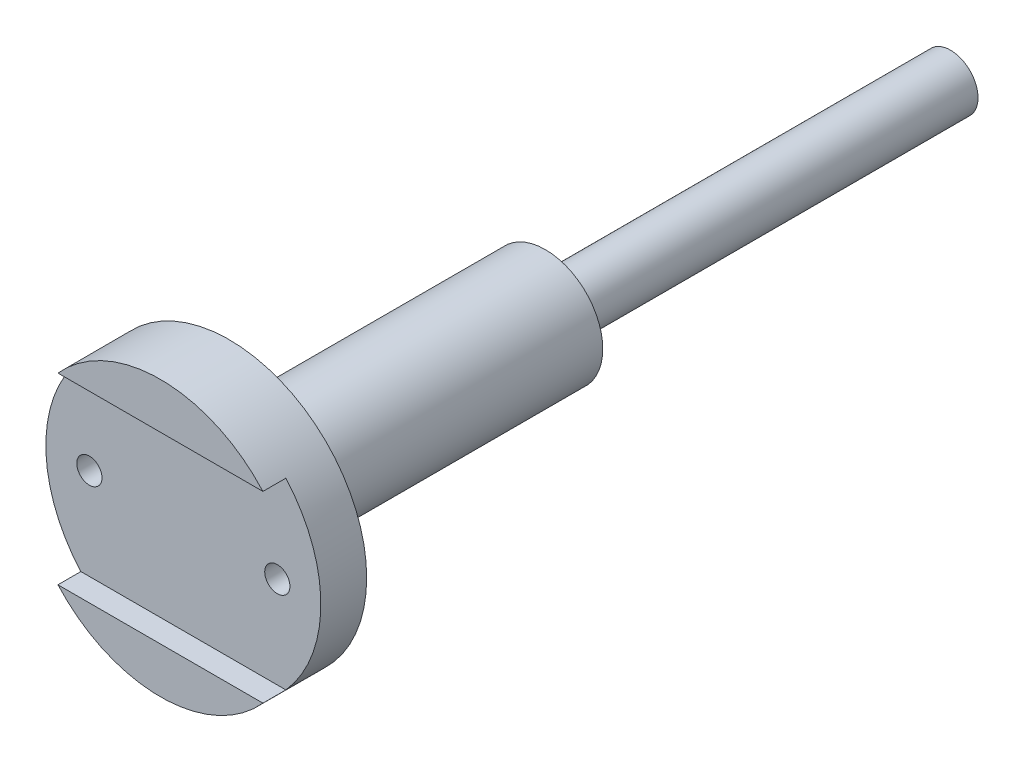
SolidWorks part; units mm, degrees
ref_plane "Plan de face" through (0, 0, 0) normal (0, 0, 1) x (1, 0, 0)
ref_plane "Plan de dessus" through (0, 0, 0) normal (0, 1, 0) x (1, 0, 0)
ref_plane "Plan de droite" through (0, 0, 0) normal (1, 0, 0) x (0, 0, -1)
sketch "Esquisse1" plane through (0, 0, 0) normal (0, 0, 1) x (1, 0, 0)
  circle A0 centre (0, 0) radius 30
  dimension "D1" = 60
extrude "Boss.-Extru.1" add sketch "Esquisse1" along normal blind 15
sketch "Esquisse2" plane through (0, 0, 0) normal (0, 0, -1) x (-1, 0, 0)
  circle A0 centre (0, 0) radius 12.5
  dimension "D1" = 25
extrude "Boss.-Extru.2" add sketch "Esquisse2" along normal blind 69
sketch "Esquisse4" plane through (0, 0, 15) normal (0, 0, 1) x (1, 0, 0)
  line L1 (115, 20) -> (-115, 20)
  line L2 (115, 20) -> (115, -20)
  line L3 (115, -20) -> (-115, -20)
  line L4 (-115, 20) -> (-115, -20)
  line L5 (115, 20) -> (-115, -20) construction
  line L6 (115, -20) -> (-115, 20) construction
  point P0 (0, 0)
  dimension "D1" = 40
  dimension "D2" = 230
extrude "Boss.-Extru.3" [suppressed] add sketch "Esquisse4" along normal blind 5
extrude "Enlèv. mat.-Extru.1" cut sketch "Esquisse4<2>" against normal blind 5
sketch "Esquisse4<2>" plane through (0, 0, 15) normal (0, 0, 1) x (1, 0, 0) same geometry as "Esquisse4"
sketch "Esquisse6" plane through (0, 0, 0) normal (0, 0, -1) x (-1, 0, 0)
  circle A2 centre (0, 0) radius 20.5
  circle A3 centre (0, 0) radius 20.5 construction
  dimension "D1" = 8
hole_wizard "Chambrage pour vis à tête hexagonale M51" positions "Esquisse15" profile "Esquisse14" counterbore size "M5" standard "Ansi Metric" end condition through all
sketch "Esquisse15" plane through (0, 0, 0) normal (0, 0, -1) x (-1, 0, 0)
  circle A0 centre (0, 0) radius 20.5 construction
  point P0 (20.5, 0)
  point P4 (-20.5, 0)
sketch "Esquisse14" plane through (-20.5, 0, 0) normal (1, 0, 0) x (0, 1, 0)
  line L0 (0, 0) -> (0, 15)
  line L1 (0, 15) -> (2.75, 15)
  line L2 (2.75, 3.605) -> (2.75, 15)
  line L3 (2.75, 3.605) -> (2.775, 3.58)
  line L4 (2.775, 3.58) -> (6.12, 3.58)
  line L5 (6.12, 3.58) -> (6.12, 0)
  line L7 (0, 0) -> (6.12, 0)
  line L9 (-2.75, 3.605) -> (-2.775, 3.58) construction
  line L11 (0, -6.35) -> (0, 107.95) construction
  dimension "Diamètre du perçage jusqu'au prochain" = 5.5
  dimension "Profondeur du perçage jusqu'au prochain" = 15
  dimension "Diamètre du chambrage" = 12.24
  dimension "Profondeur du chambrage" = 3.58
  dimension "Diamètre du fraisage milieu" = 5.55
  dimension "Angle du fraisage milieu" = 90
sketch "Esquisse17" plane through (0, 0, -69) normal (0, 0, -1) x (-1, 0, 0)
  circle A0 centre (0, 0) radius 6
  dimension "D1" = 12
extrude "Boss.-Extru.4" add sketch "Esquisse17" along normal blind 88.38
sketch "Esquisse18" plane through (0, 0, -157.38) normal (0, 0, -1) x (-1, 0, 0)
  line L0 (6.9654, 0) -> (-3.391, 0) construction
  line L1 (-3.391, 1.5) -> (6.9654, 1.5)
  line L2 (-3.391, 1.5) -> (-3.391, -1.5)
  line L3 (-3.391, -1.5) -> (6.9654, -1.5)
  line L4 (6.9654, 1.5) -> (6.9654, -1.5)
  line L5 (-3.391, 1.5) -> (6.9654, -1.5) construction
  line L6 (-3.391, -1.5) -> (6.9654, 1.5) construction
  point P0 (-0.771, 0)
  dimension "D1" = 3
  dimension "D2" = 2.62
extrude "Enlèv. mat.-Extru.2" cut sketch "Esquisse18" against normal blind 3
